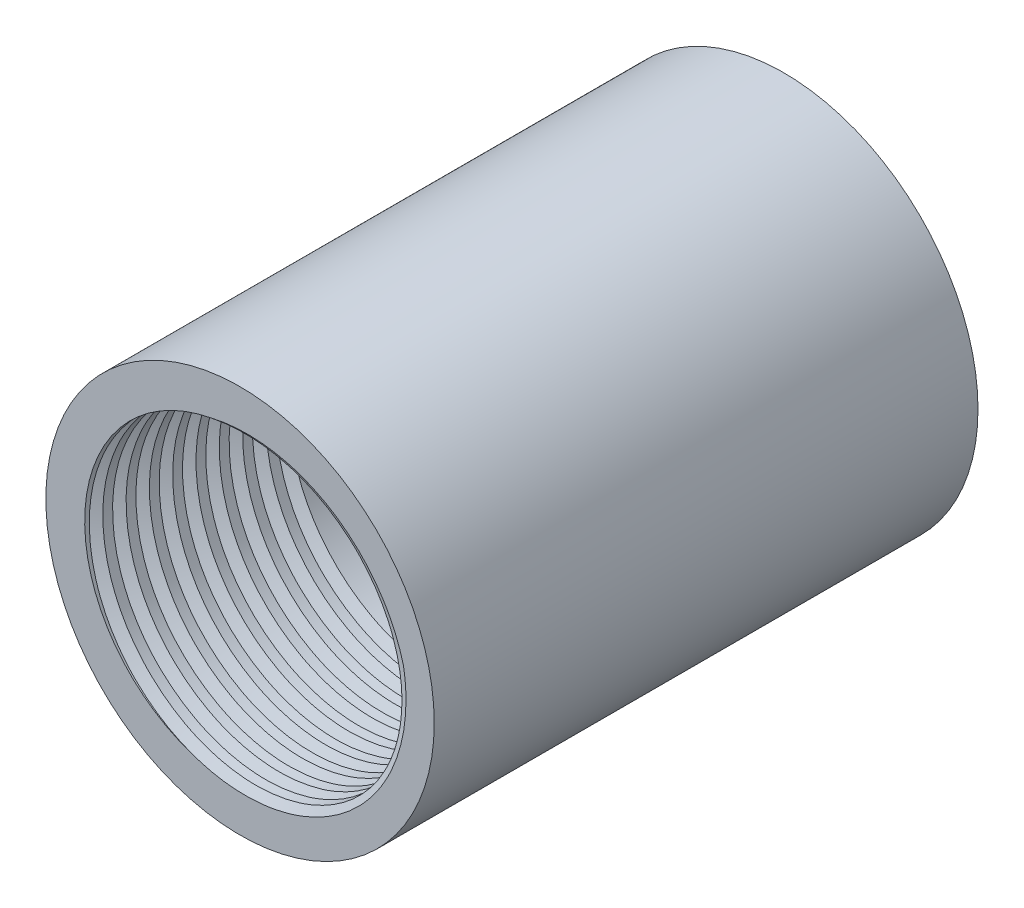
SolidWorks part; units mm, degrees
ref_plane "前视基准面" through (0, 0, 0) normal (0, 0, 1) x (1, 0, 0)
ref_plane "上视基准面" through (0, 0, 0) normal (0, 1, 0) x (1, 0, 0)
ref_plane "右视基准面" through (0, 0, 0) normal (1, 0, 0) x (0, 0, -1)
sketch "草图1" plane through (0, 0, 0) normal (0, 0, 1) x (1, 0, 0)
  circle A0 centre (0, 0) radius 10
  circle A1 centre (0, 0) radius 12.5
  dimension "D1" = 20
  dimension "D2" = 25
extrude "凸台-拉伸1" add sketch "草图1" along normal blind 35
sketch "草图2" plane through (0, 0, 35) normal (0, 0, 1) x (1, 0, 0)
  circle A0 centre (0, 0) radius 10
  dimension "D1" = 20
curve "螺旋线/涡状线1" pitch 1.5 height 13.5 radius 10 centre (0, 0, 35) axis (0, 0, -1) start towards (1, 0, 0)
sketch "草图3" plane through (0, 0, 0) normal (0, 1, 0) x (1, 0, 0)
  line L1 (10.7484, -34.9512) -> (9.5835, -34.3763)
  line L2 (9.5835, -34.3763) -> (9.6681, -35.6726)
  line L3 (9.6681, -35.6726) -> (10.7484, -34.9512)
  circle A0 centre (10, -35) radius 0.375 construction
  dimension "D1" = 0.75
sweep "切除-扫描1" cut profiles "草图3" path "螺旋线/涡状线1" align with end faces yes
